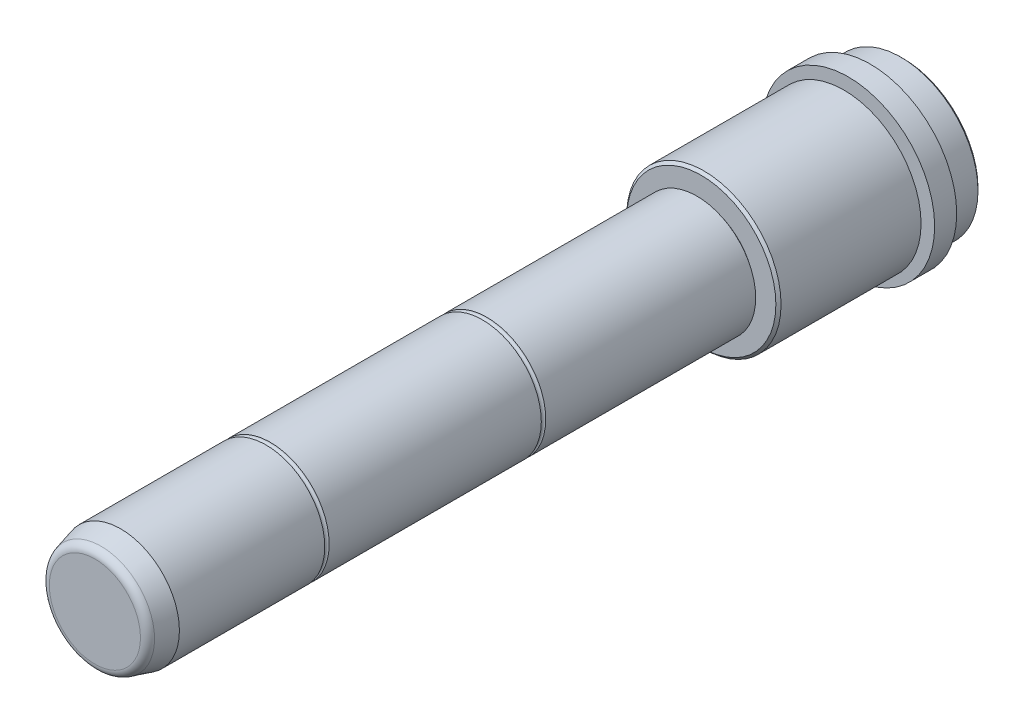
SolidWorks part; units mm, degrees
ref_plane "Płaszczyzna przednia" through (0, 0, 0) normal (0, 0, 1) x (1, 0, 0)
ref_plane "Płaszczyzna górna" through (0, 0, 0) normal (0, 1, 0) x (1, 0, 0)
ref_plane "Płaszczyzna prawa" through (0, 0, 0) normal (1, 0, 0) x (0, 0, -1)
sketch "Szkic1" plane through (0, 0, 0) normal (1, 0, 0) x (0, 0, -1)
  line L0 (-9, 0) -> (-9, 21)
  line L1 (-9, 21) -> (0, 21)
  line L2 (0, 21) -> (0, 0)
  line L3 (0, 0) -> (-9, 0)
  line L4 (0, 0) -> (-9, 0) construction
sketch "Szkic2" plane through (0, 0, 0) normal (1, 0, 0) x (0, 0, -1)
  line L0 (-0.7071, 21) -> (0, 20.2929)
  line L1 (0, 20.2929) -> (0, 21)
  line L2 (0, 21) -> (-0.7071, 21)
  line L3 (0, 0) -> (-9, 0) construction
sketch "Szkic3" plane through (0, 0, 0) normal (1, 0, 0) x (0, 0, -1)
  line L0 (-9, 18.9) -> (-7.8, 18.9)
  line L1 (-7.8, 18.9) -> (-7.8, 21)
  line L2 (-7.8, 21) -> (-9, 21)
  line L3 (-9, 21) -> (-9, 18.9)
  line L4 (0, 0) -> (-9, 0) construction
sketch "Szkic4" plane through (0, 0, 0) normal (1, 0, 0) x (0, 0, -1)
  line L0 (-15, 0) -> (-15, 23.5)
  line L1 (-15, 23.5) -> (-9, 23.5)
  line L2 (-9, 23.5) -> (-9, 0)
  line L3 (-9, 0) -> (-15, 0)
  line L4 (-9, 0) -> (-15, 0) construction
sketch "Szkic5" plane through (0, 0, 0) normal (1, 0, 0) x (0, 0, -1)
  line L0 (-55, 0) -> (-55, 21)
  line L1 (-55, 21) -> (-15, 21)
  line L2 (-15, 21) -> (-15, 0)
  line L3 (-15, 0) -> (-55, 0)
  line L4 (-15, 0) -> (-55, 0) construction
sketch "Szkic6" plane through (0, 0, 0) normal (1, 0, 0) x (0, 0, -1)
  line L0 (-16.2, 18.9) -> (-15, 18.9)
  line L1 (-15, 18.9) -> (-15, 21)
  line L2 (-15, 21) -> (-16.2, 21)
  line L3 (-16.2, 21) -> (-16.2, 18.9)
  line L4 (-15, 0) -> (-61, 0) construction
sketch "Szkic7" plane through (0, 0, 0) normal (1, 0, 0) x (0, 0, -1)
  line L0 (-55, 20.2929) -> (-54.2929, 21)
  line L1 (-54.2929, 21) -> (-55, 21)
  line L2 (-55, 21) -> (-55, 20.2929)
  line L3 (-9, 0) -> (-55, 0) construction
sketch "Szkic8" plane through (0, 0, 0) normal (1, 0, 0) x (0, 0, -1)
  line L0 (-220, 0) -> (-220, 16)
  line L1 (-220, 16) -> (-55, 16)
  line L2 (-55, 16) -> (-55, 0)
  line L3 (-55, 0) -> (-220, 0)
  line L4 (-55, 0) -> (-220, 0) construction
sketch "Szkic9" plane through (0, 0, 0) normal (1, 0, 0) x (0, 0, -1)
  line L0 (-56.2, 14.4) -> (-55, 14.4)
  line L1 (-55, 14.4) -> (-55, 16)
  line L2 (-55, 16) -> (-56.2, 16)
  line L3 (-56.2, 16) -> (-56.2, 14.4)
  line L4 (-55, 0) -> (-220, 0) construction
sketch "Szkic10" plane through (0, 0, 0) normal (1, 0, 0) x (0, 0, -1)
  line L0 (-220, 14.1244) -> (-213, 16)
  line L1 (-213, 16) -> (-220, 16)
  line L2 (-220, 16) -> (-220, 14.1244)
  line L3 (-55, 0) -> (-220, 0) construction
sketch "Szkic11" plane through (0, 0, 0) normal (1, 0, 0) x (0, 0, -1)
  line L0 (-218.3323, 14.5712) -> (-220, 14.1244)
  line L1 (-220, 14.1244) -> (-220, 12.3979)
  line L2 (-55, 0) -> (-220, 0) construction
  arc A0 (-220, 12.3979) -> (-218.3323, 14.5712) centre (-217.75, 12.3979) cw
sketch "Szkic12" plane through (0, 0, 0) normal (1, 0, 0) x (0, 0, -1)
  line L0 (-172.2571, 16) -> (-173.4571, 16)
  line L1 (-172.2571, 0) -> (-173.4571, 0) construction
  arc A0 (-173.4571, 16) -> (-172.2571, 16) centre (-172.8571, 16) ccw
sketch "Szkic13" plane through (0, 0, 0) normal (1, 0, 0) x (0, 0, -1)
  line L0 (-113.3286, 16) -> (-114.5286, 16)
  line L1 (-113.3286, 0) -> (-114.5286, 0) construction
  arc A0 (-114.5286, 16) -> (-113.3286, 16) centre (-113.9286, 16) ccw
ref_plane "Płaszczyzna1" through (0, 0, 9) normal (0, 0, 1) x (1, 0, 0)
revolve "Obrót1" add sketch "Szkic1" angle 360 about L4 reverse direction yes
revolve "Wycięcie-obrót1" cut sketch "Szkic2" angle 360 about L3 reverse direction yes
revolve "Wycięcie-obrót2" cut sketch "Szkic3" angle 360 about L4 reverse direction yes
revolve "Obrót2" add sketch "Szkic4" angle 360 about L4 reverse direction yes
revolve "Obrót3" add sketch "Szkic5" angle 360 about L4 reverse direction yes
revolve "Wycięcie-obrót3" cut sketch "Szkic6" angle 360 about L4 reverse direction yes
revolve "Wycięcie-obrót4" cut sketch "Szkic7" angle 360 about L3 reverse direction yes
revolve "Obrót4" add sketch "Szkic8" angle 360 about L4 reverse direction yes
revolve "Wycięcie-obrót5" cut sketch "Szkic9" angle 360 about L4 reverse direction yes
revolve "Wycięcie-obrót6" cut sketch "Szkic10" angle 360 about L3 reverse direction yes
revolve "Wycięcie-obrót7" cut sketch "Szkic11" angle 360 about L2 reverse direction yes
revolve "Wycięcie-obrót8" cut sketch "Szkic12" angle 360 about L1 reverse direction yes
revolve "Wycięcie-obrót9" cut sketch "Szkic13" angle 360 about L1 reverse direction yes
ref_plane "IP1 XY" through (0, 0, 9) normal (0, 0, 1) x (1, 0, 0)
ref_plane "IP1 XZ" through (0, 0, 0) normal (0, -1, 0) x (-1, 0, 0)
ref_plane "IP1 YZ" through (0, 0, 0) normal (1, 0, 0) x (0, 0, -1)
ref_axis "IP1 X" through (-80.9, 0, 9) along (1, 0, 0)
ref_axis "IP1 Y" through (0, -50, 9) along (0, 1, 0)
ref_axis "IP1 Z" through (0, 0, 80.9) along (0, 0, -1)
sketch3d "IP1"
  point P0 (0, 0, 9)
